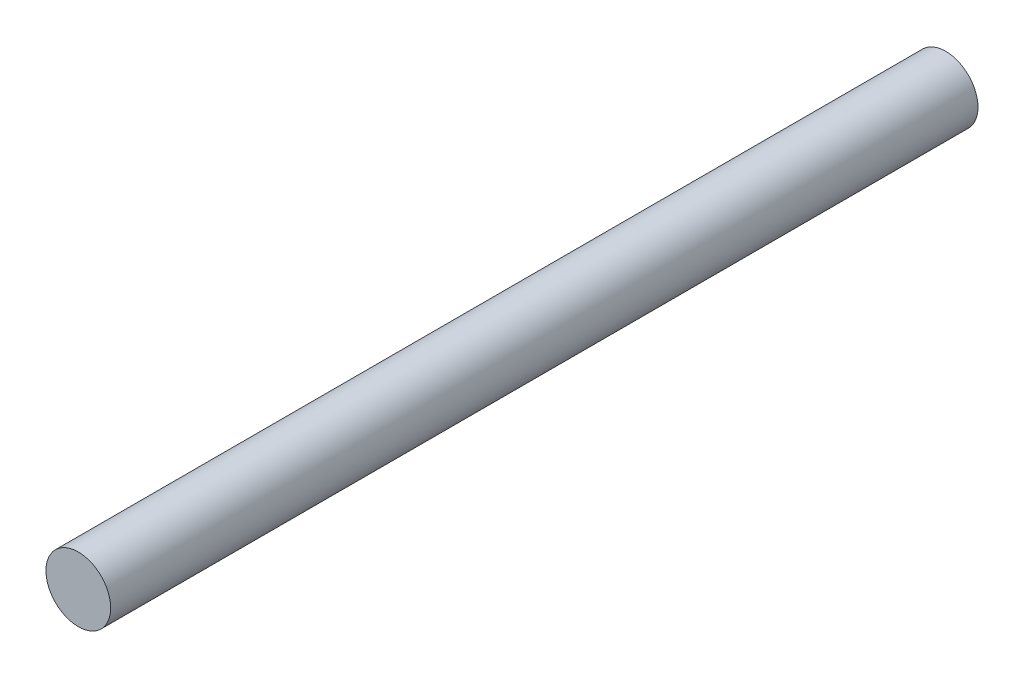
SolidWorks part; units mm, degrees
material "AISI 1010 Steel, hot rolled bar"
ref_plane "Front Plane" through (0, 0, 0) normal (0, 0, 1) x (1, 0, 0)
ref_plane "Top Plane" through (0, 0, 0) normal (0, 1, 0) x (1, 0, 0)
ref_plane "Right Plane" through (0, 0, 0) normal (1, 0, 0) x (0, 0, -1)
sketch "Sketch2" plane through (0, 0, 0) normal (0, 0, 1) x (1, 0, 0)
  circle A0 centre (0, 0) radius 6.35
  dimension "D1" = 12.7
extrude "Boss-Extrude1" add sketch "Sketch2" along normal blind 170.18
